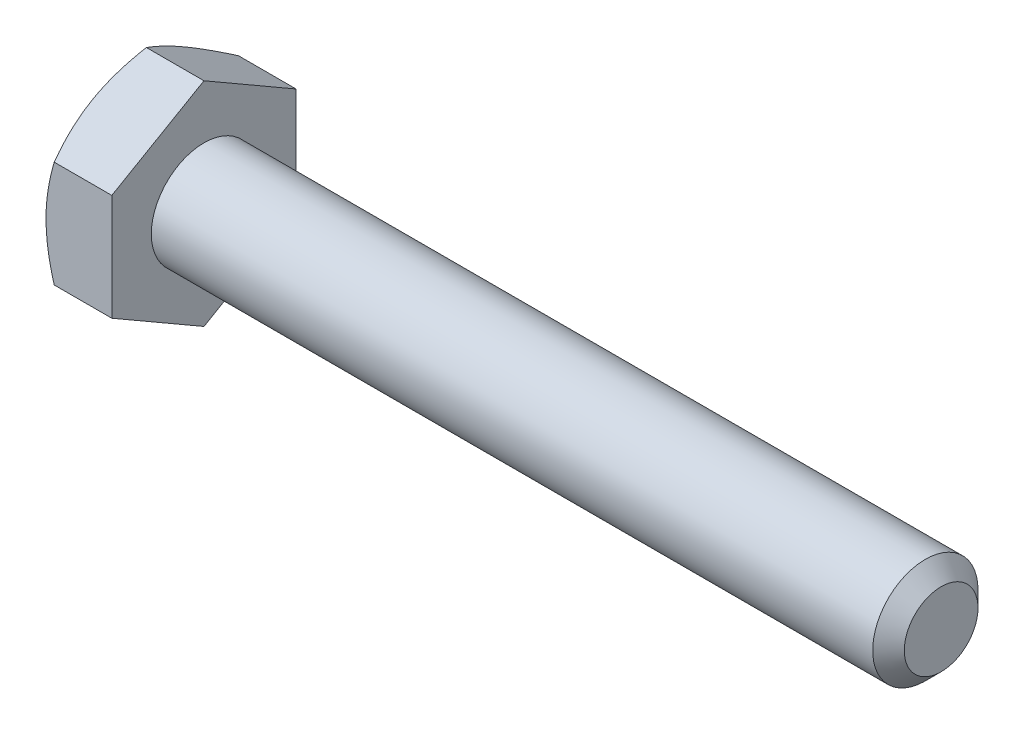
SolidWorks part; units mm, degrees
material "6061-T6 (SS)"
ref_plane "Front Plane" through (0, 0, 0) normal (0, 0, 1) x (1, 0, 0)
ref_plane "Top Plane" through (0, 0, 0) normal (0, 1, 0) x (1, 0, 0)
ref_plane "Right Plane" through (0, 0, 0) normal (1, 0, 0) x (0, 0, -1)
sketch "Sketch1" plane through (0, 0, 0) normal (0, 0, 1) x (1, 0, 0)
  line L0 (-24.2094, 0) -> (24.2094, 0) construction
  line L1 (24.2094, 3.175) -> (24.2094, -3.175) construction
  line L2 (-20.2406, 5.5562) -> (-20.2406, -5.5562) construction
  line L3 (-24.2094, 5.5562) -> (-24.2094, -5.5562) construction
  line L4 (25.4, -3.3125) -> (24.765, -2.2126) construction
  line L5 (24.765, -2.2126) -> (24.13, -3.3125) construction
  line L6 (24.13, -3.3125) -> (25.4, -3.3125) construction
  line L7 (25.3206, -3.175) -> (24.2094, -3.175) construction
  line L8 (24.765, -3.3125) -> (24.765, -3.175) construction
  line L9 (24.765, -3.175) -> (24.765, -2.3501) construction
  line L10 (24.765, -2.3501) -> (24.765, -2.2126) construction
  line L15 (24.8444, -2.3501) -> (24.6856, -2.3501)
  line L16 (25.3603, -3.2437) -> (24.1697, -3.2437)
  line L17 (24.6856, -2.3501) -> (24.1697, -3.2437)
  line L18 (24.8444, -2.3501) -> (25.3603, -3.2437)
  point P9 (-20.2406, 0)
  point P10 (19.2705, -3.175)
  point P24 (24.765, -3.2437)
  dimension "Head Ht" = 3.9688
  dimension "D1" = 4.9389
  dimension "Pitch" = 1.27
  dimension "D3" = 0.1588
  dimension "Head Width" = 11.1125
  dimension "Length" = 44.45
  dimension "Screw Size" = 6.35
ref_plane "Plane2" through (24.2094, 0, 0) normal (1, 0, 0) x (0, 0, -1)
sketch "Sketch5" plane through (24.2094, 0, 0) normal (1, 0, 0) x (0, 0, -1)
  circle A0 centre (0, 0) radius 3.175
extrude "Boss-Extrude3" add sketch "Sketch5" against normal up to vertex (44.45 mm away) up to point (-20.2406, 0, 0)
chamfer "Chamfer1" distance 0.9525 angle 45 1 edges at (24.2094, 0, -3.175)
sketch "Sketch6" plane through (-20.2406, 0, 0) normal (-1, 0, 0) x (0, 0, 1)
  line L0 (0, 5.5562) -> (0, -5.5562) construction
  line L1 (5.5562, 3.2079) -> (0, 6.4158)
  line L2 (0, 6.4158) -> (-5.5563, 3.2079)
  line L3 (-5.5563, 3.2079) -> (-5.5562, -3.2079)
  line L4 (-5.5562, -3.2079) -> (0, -6.4158)
  line L5 (0, -6.4158) -> (5.5563, -3.2079)
  line L6 (5.5563, -3.2079) -> (5.5562, 3.2079)
  circle A0 centre (0, 0) radius 5.5562 construction
extrude "Boss-Extrude4" add sketch "Sketch6" along normal up to vertex (3.9688 mm away) up to point (-24.2094, -5.5562, 0)
sketch "Sketch7" plane through (-24.2094, 0, 0) normal (-1, 0, 0) x (0, 0, 1)
  circle A0 centre (0, 0) radius 5.5562 construction
  circle A1 centre (0, 0) radius 5.5562
sketch "Sketch8" plane through (-24.2094, 0, 0) normal (-1, 0, 0) x (0, 0, 1)
  circle A0 centre (0, 0) radius 5.5562 construction
  circle A1 centre (0, 0) radius 5.5562
extrude "Cut-Extrude3" cut sketch "Sketch8" against normal through all draft 60 flip side to cut
split "Split1" [suppressed] bodies to split 113
sketch "Sketch9" [suppressed] plane through (24.2094, 0, 0) normal (1, 0, 0) x (0, 0, -1)
  circle A0 centre (0, 0) radius 3.175 construction
  circle A1 centre (0, 0) radius 3.175
curve "Helix/Spiral1" [suppressed] pitch 1.27 height 45.72 turns 36
sketch "Sketch10" [suppressed] plane through (0, 0, 0) normal (0, 0, 1) x (1, 0, 0)
  line L8 (24.8444, -2.3501) -> (24.6856, -2.3501) construction
  line L9 (24.6856, -2.3501) -> (24.1697, -3.2437) construction
  line L10 (25.3603, -3.2437) -> (24.1697, -3.2437) construction
  line L11 (24.8444, -2.3501) -> (25.3603, -3.2437) construction
  line L12 (24.8444, -2.3501) -> (24.6856, -2.3501)
  line L13 (24.6856, -2.3501) -> (24.1697, -3.2437)
  line L14 (25.3603, -3.2437) -> (24.1697, -3.2437)
  line L15 (24.8444, -2.3501) -> (25.3603, -3.2437)
sweep "Cut-Sweep1" [suppressed] cut profiles "Sketch10" path "Helix/Spiral1"
combine bodies "Combine1" [suppressed] operation type add bodies to combine 119 120
sketch "Sketch11" [suppressed] plane through (-20.2406, 0, 0) normal (1, 0, 0) x (0, 0, -1)
  line L0 (0, 5.5562) -> (0, -5.5562) construction
  circle A0 centre (0, 0) radius 3.4925
  point P3 (0, -3.4925)
  dimension "D1" = 0.3175
extrude "Boss-Extrude5" [suppressed] add sketch "Sketch11" along normal through all draft 45
equation "\"D3@Helix/Spiral1\"= \"Length@Sketch1\" + \"Pitch@Sketch1\""
equation "\"D1@Chamfer1\" = \"Pitch@Sketch1\" * .75"
equation "\"D4@Helix/Spiral1\"=\"Pitch@Sketch1\""
equation "\"D3@Sketch1\" = \"Pitch@Sketch1\" / 8"
equation "\"D1@Sketch11\"=\"Pitch@Sketch1\"/4"
